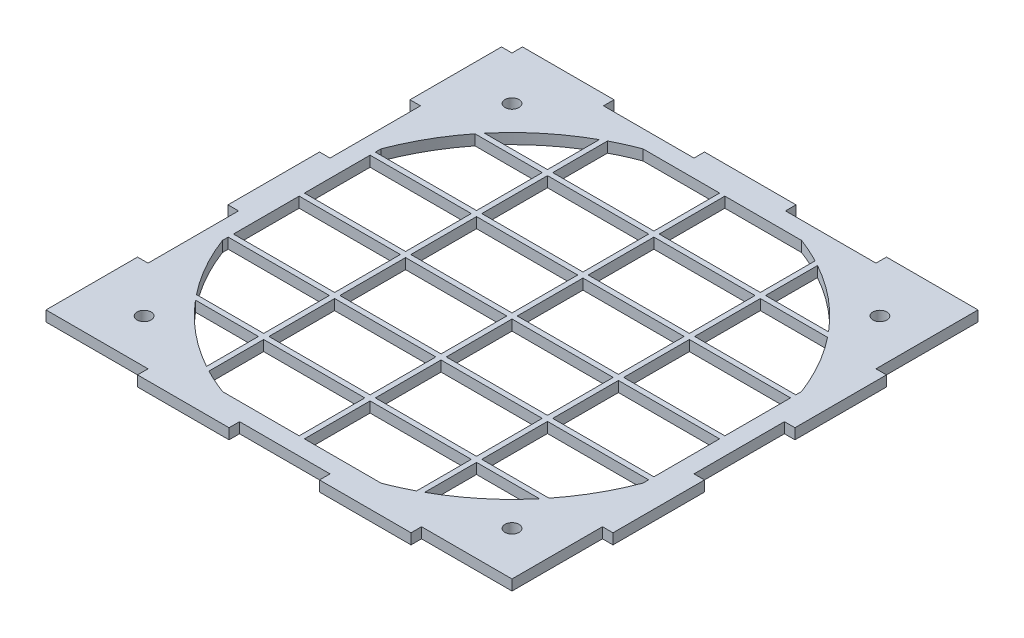
SolidWorks part; units mm, degrees
ref_plane "Front Plane" through (0, 0, 0) normal (0, 0, 1) x (1, 0, 0)
ref_plane "Top Plane" through (0, 0, 0) normal (0, 1, 0) x (1, 0, 0)
ref_plane "Right Plane" through (0, 0, 0) normal (1, 0, 0) x (0, 0, -1)
sketch "Sketch1" plane through (0, 0, 0) normal (0, 1, 0) x (1, 0, 0)
  line L0 (0, 60) -> (0, 65) construction
  line L1 (-60, 0) -> (-65, 0) construction
  line L2 (0, -60) -> (0, -65) construction
  line L7 (22.6278, -60) -> (-22.6278, -60)
  line L8 (60, -22.6278) -> (60, 22.6278)
  line L21 (22.6278, 60) -> (-22.6278, 60)
  line L45 (-60, -22.6278) -> (-60, 22.6278)
  line L46 (60, -60) -> (-60, 60) construction
  line L99 (60, 60) -> (-60, -60) construction
  line L116 (65, 38.88) -> (68, 38.88)
  line L117 (-65, -38.88) -> (-65, -13.06)
  line L118 (68, 38.88) -> (68, 12.76)
  line L119 (68, 12.76) -> (65, 12.76)
  line L120 (60, 0) -> (65, 0) construction
  line L121 (-13.06, 65) -> (-38.88, 65)
  line L122 (-38.88, 65) -> (-38.88, 68)
  line L123 (-13.06, 65) -> (-13.06, 68)
  line L124 (-13.06, 68) -> (13.06, 68)
  line L125 (13.06, 65) -> (13.06, 68)
  line L126 (38.88, 65) -> (38.88, 68)
  line L127 (38.88, 68) -> (65, 68)
  line L128 (38.88, 65) -> (13.06, 65)
  line L129 (-65, 66.5) -> (-39.18, 66.5) construction
  line L130 (-39.18, 66.5) -> (-38.88, 66.5) construction
  line L131 (-65, 38.88) -> (-68, 38.88)
  line L132 (-65, 13.06) -> (-68, 13.06)
  line L133 (-65, -13.06) -> (-68, -13.06)
  line L134 (-68, 13.06) -> (-68, -13.06)
  line L135 (-65, -38.88) -> (-68, -38.88)
  line L136 (-68, -65) -> (-68, -38.88)
  line L137 (-65, 13.06) -> (-65, 38.88)
  line L138 (-38.88, -65) -> (-64.7, -65)
  line L139 (65, 12.76) -> (65, -13.06)
  line L140 (65, -13.06) -> (68, -13.06)
  line L141 (68, -13.06) -> (68, -39.18)
  line L142 (68, -39.18) -> (65, -39.18)
  line L143 (65, -39.18) -> (65, -65)
  line L144 (65, -65) -> (39.18, -65)
  line L145 (39.18, -65) -> (39.18, -68)
  line L146 (39.18, -68) -> (13.06, -68)
  line L147 (13.06, -68) -> (13.06, -65)
  line L148 (13.06, -65) -> (-12.76, -65)
  line L149 (-12.76, -65) -> (-12.76, -68)
  line L150 (-12.76, -68) -> (-38.88, -68)
  line L151 (-38.88, -68) -> (-38.88, -65)
  line L152 (-64.7, -65) -> (-68, -65)
  line L153 (65, 68) -> (65, 64.7)
  line L154 (65, 64.7) -> (65, 38.88)
  line L155 (-38.88, 68) -> (-65, 68)
  line L156 (-65, 68) -> (-65, 65)
  line L157 (-65, 65) -> (-68, 65)
  line L158 (-68, 65) -> (-68, 38.88)
  arc A9 (-60, -22.6278) -> (-22.6278, -60) centre (0, 0) ccw
  arc A10 (-22.6278, 60) -> (-60, 22.6278) centre (0, 0) ccw
  arc A11 (60, 22.6278) -> (22.6278, 60) centre (0, 0) ccw
  arc A12 (22.6278, -60) -> (60, -22.6278) centre (0, 0) ccw
  dimension "D3" = 0.3
  dimension "D2" = 128.25
  dimension "D1" = 120
  dimension "D4" = 3
  dimension "D5" = 130
extrude "Boss-Extrude1" add sketch "Sketch1" along normal blind 3
sketch "Sketch2" plane through (0, 3, 0) normal (0, 1, 0) x (1, 0, 0)
  line L1 (-65, 61.5) -> (65, 61.5)
  line L2 (-65, 61.5) -> (-65, 60)
  line L3 (-65, 60) -> (65, 60)
  line L4 (65, 61.5) -> (65, 60)
  line L5 (-22.6278, -60) -> (22.6278, -60) construction
  line L7 (-65, 41.25) -> (-65, 39.75)
  line L8 (-65, 41.25) -> (65, 41.25)
  line L9 (65, 41.25) -> (65, 39.75)
  line L10 (-65, 39.75) -> (65, 39.75)
  line L11 (-65, 21) -> (-65, 19.5)
  line L12 (-65, 21) -> (65, 21)
  line L13 (65, 21) -> (65, 19.5)
  line L14 (-65, 19.5) -> (65, 19.5)
  line L15 (-65, 0.75) -> (-65, -0.75)
  line L16 (-65, 0.75) -> (65, 0.75)
  line L17 (65, 0.75) -> (65, -0.75)
  line L18 (-65, -0.75) -> (65, -0.75)
  line L19 (-65, -19.5) -> (-65, -21)
  line L20 (-65, -19.5) -> (65, -19.5)
  line L21 (65, -19.5) -> (65, -21)
  line L22 (-65, -21) -> (65, -21)
  line L23 (-65, -39.75) -> (-65, -41.25)
  line L24 (-65, -39.75) -> (65, -39.75)
  line L25 (65, -39.75) -> (65, -41.25)
  line L26 (-65, -41.25) -> (65, -41.25)
  line L27 (-65, -60) -> (-65, -61.5)
  line L28 (-65, -60) -> (65, -60)
  line L29 (65, -60) -> (65, -61.5)
  line L30 (-65, -61.5) -> (65, -61.5)
  line L57 (22.6278, 60) -> (-22.6278, 60) construction
  line L60 (-65, 38.88) -> (-65, 13.06) construction
  line L61 (65, 38.88) -> (65, 68) construction
  dimension "D1" = 1.5
  dimension "D2" = 7
extrude "Boss-Extrude2" add sketch "Sketch2" against normal through all
sketch "Sketch3" plane through (0, 3, 0) normal (0, 1, 0) x (1, 0, 0)
  line L1 (60, 0.75) -> (60, 19.5) construction
  line L2 (-60, -60) -> (-61.5, -60)
  line L3 (-60, -60) -> (-60, 60)
  line L4 (-60, 60) -> (-61.5, 60)
  line L5 (-61.5, -60) -> (-61.5, 60)
  line L6 (-60, -0.75) -> (-60, -19.5) construction
  line L8 (-29.625, -60) -> (-29.625, 60)
  line L9 (-29.625, -60) -> (-31.125, -60)
  line L10 (-31.125, -60) -> (-31.125, 60)
  line L11 (-29.625, 60) -> (-31.125, 60)
  line L12 (0.75, -60) -> (0.75, 60)
  line L13 (0.75, -60) -> (-0.75, -60)
  line L14 (-0.75, -60) -> (-0.75, 60)
  line L15 (0.75, 60) -> (-0.75, 60)
  line L16 (31.125, -60) -> (31.125, 60)
  line L17 (31.125, -60) -> (29.625, -60)
  line L18 (29.625, -60) -> (29.625, 60)
  line L19 (31.125, 60) -> (29.625, 60)
  line L20 (61.5, -60) -> (61.5, 60)
  line L21 (61.5, -60) -> (60, -60)
  line L22 (60, -60) -> (60, 60)
  line L23 (61.5, 60) -> (60, 60)
  line L80 (22.6278, 60) -> (-22.6278, 60) construction
  line L81 (-22.6278, -60) -> (22.6278, -60) construction
  dimension "D2" = 1.5
  dimension "D1" = 5
extrude "Boss-Extrude3" add sketch "Sketch3" against normal through all contours L16 L19 L18 L17 | L20 L23 L22 L21 | L14 L15 L12 L13 | L10 L11 L8 L9 | L3 L4 L5 L2 region at (30.375, 3, 0)
sketch "Sketch4" plane through (0, 3, 0) normal (0, 1, 0) x (1, 0, 0)
  line L5 (-52.5, -52.5) -> (52.5, -52.5) construction
  line L6 (-52.5, -52.5) -> (-52.5, 52.5) construction
  line L7 (-52.5, 52.5) -> (52.5, 52.5) construction
  line L8 (52.5, -52.5) -> (52.5, 52.5) construction
  line L11 (65, 65) -> (-65, 65) construction
  line L12 (65, 38.88) -> (65, 68) construction
  circle A2 centre (-52.5, 52.5) radius 2
  circle A3 centre (52.5, 52.5) radius 2
  circle A4 centre (52.5, -52.5) radius 2
  circle A5 centre (-52.5, -52.5) radius 2
  point P2 (-52.5, 0)
  point P8 (0, 52.5)
  point P23 (0, 65)
  dimension "D2" = 4
  dimension "D1" = 105
extrude "Cut-Extrude1" cut sketch "Sketch4" against normal through all
